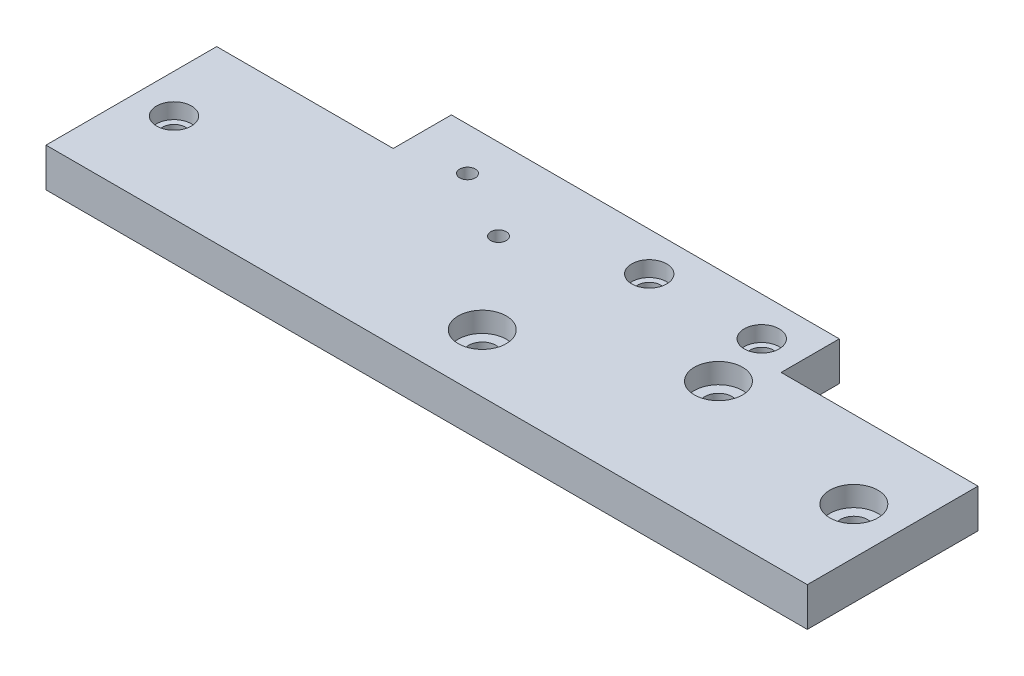
SolidWorks part; units mm, degrees
other "标注1"
sketch "草图3" plane through (0, 5, 29.5) normal (-0.6417, 0.7662, 0.0339) x (0.7661, 0.6384, 0.0747)
ref_plane "前视基准面" through (0, 0, 0) normal (0, 0, 1) x (1, 0, 0)
ref_plane "上视基准面" through (0, 0, 0) normal (0, 1, 0) x (1, 0, 0)
ref_plane "右视基准面" through (0, 0, 0) normal (1, 0, 0) x (0, 0, -1)
other "Configuration Table"
sketch "草图1" plane through (0, 0, 0) normal (0, 1, 0) x (1, 0, 0)
  line L33 (-50, -29.5) -> (0, -29.5)
  line L34 (-50, -29.5) -> (-50, 0)
  line L36 (0, -29.5) -> (0, 0)
  line L37 (-50, 0) -> (0, 0)
  line L38 (-72.75, -7.5) -> (25.3755, -7.5)
  line L39 (-72.75, -7.5) -> (-72.75, -29.5)
  line L40 (-72.75, -29.5) -> (25.3755, -29.5)
  line L41 (25.3755, -7.5) -> (25.3755, -29.5)
  circle A7 centre (19.3755, -17.5) radius 1.75
  circle A8 centre (-3.0745, -12.5) radius 1.75
  circle A9 centre (19.3755, -17.5) radius 3.1
  circle A10 centre (-3.0745, -12.5) radius 3.1
  circle A11 centre (35.25, -22) radius 1.0216
  circle A12 centre (-24.0208, -22) radius 3.1
  circle A13 centre (-19.5, -5) radius 2.25
  circle A14 centre (-19.5, -5) radius 1.5
  circle A15 centre (-5, -5) radius 1.5
  circle A16 centre (-5, -5) radius 2.25
  circle A17 centre (-24.0208, -22) radius 1.75
  circle A18 centre (-67.75, -18) radius 1.5
  circle A19 centre (-67.75, -18) radius 2.25
  circle A20 centre (-42.4208, -5.5) radius 1
  circle A21 centre (-33.4208, -10.5) radius 1
  point P0 (-90.6464, 22.0667)
  dimension "D1" = 3.5
  dimension "D2" = 29.5
  dimension "D3" = 6.2
  dimension "D4" = 50
  dimension "D5" = 16.5
  dimension "D9" = 3
  dimension "D10" = 4.5
  dimension "D13" = 23
  dimension "D15" = 10
  dimension "D18" = 2
  dimension "D6" = 23
  dimension "D7" = 6
  dimension "D8" = 2.5
  dimension "D11" = 14.5
  dimension "D12" = 5
  dimension "D14" = 5
  dimension "D16" = 5
  dimension "D17" = 5
extrude "凸台-拉伸1" add sketch "草图1" along normal blind 5 contours L34 | L37 L36 L33 L34 | L38 L41 L40 L39 | A20 | A21 region at (-61.1658, 0, 18.5164)
extrude "切除-拉伸2" cut sketch "草图1<20>" along normal through all contours A14 | A15 | A18 | A21
sketch "草图1<20>" plane through (0, 0, 0) normal (0, 1, 0) x (1, 0, 0) same geometry as "草图1"
extrude "切除-拉伸3" cut sketch "草图1<22>" against normal blind 2 from surface contours A13 | A16 | A19 starting at face at (-5, 5, 6.5)
sketch "草图1<22>" plane through (0, 0, 0) normal (0, 1, 0) x (1, 0, 0) same geometry as "草图1"
extrude "切除-拉伸4" cut sketch "草图1<23>" against normal blind 2.6 from surface contours A10 | A9 | A12 starting at face at (-67.75, 5, 20.25)
sketch "草图1<23>" plane through (0, 0, 0) normal (0, 1, 0) x (1, 0, 0) same geometry as "草图1"
extrude "切除-拉伸6" cut sketch "草图1<24>" against normal through all from surface contours A8 | A7 | A17 starting at face at (-24.0208, 5, 25.1)
sketch "草图1<24>" plane through (0, 0, 0) normal (0, 1, 0) x (1, 0, 0) same geometry as "草图1"
